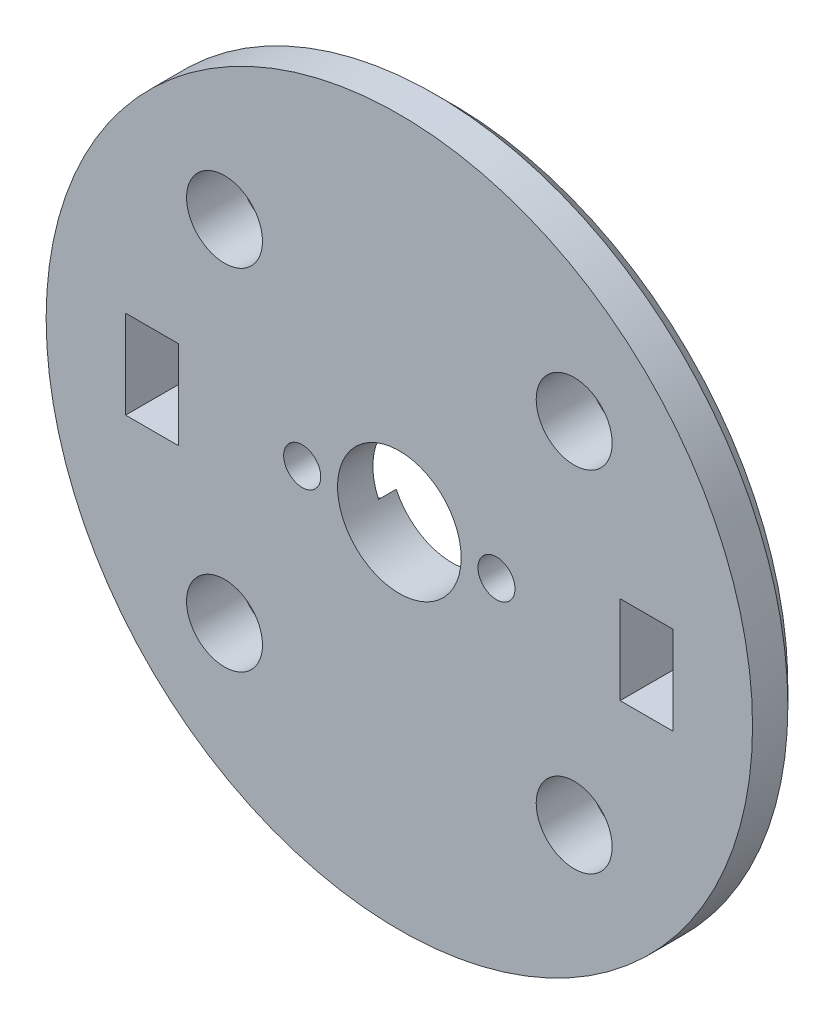
SolidWorks part; units mm, degrees
ref_plane "前视基准面" through (0, 0, 0) normal (0, 0, 1) x (1, 0, 0)
ref_plane "上视基准面" through (0, 0, 0) normal (0, 1, 0) x (1, 0, 0)
ref_plane "右视基准面" through (0, 0, 0) normal (1, 0, 0) x (0, 0, -1)
sketch "草图1" plane through (0, 0, 0) normal (0, 0, 1) x (1, 0, 0)
  circle A0 centre (0, 0) radius 20
  dimension "D1" = 40
extrude "凸台-拉伸1" add sketch "草图1" along normal blind 2
sketch "草图2" plane through (0, 0, 2) normal (0, 0, 1) x (1, 0, 0)
  circle A0 centre (0, 0) radius 3.5
  dimension "D1" = 7
extrude "切除-拉伸1" cut sketch "草图2" against normal blind 2
sketch "草图3" plane through (0, 0, 2) normal (0, 0, 1) x (1, 0, 0)
  circle A0 centre (-5.5, 0) radius 1.05
  circle A1 centre (5.5, 0) radius 1.05
  circle A2 centre (0, 0) radius 3.5 construction
  dimension "D1" = 2.1
  dimension "D2" = 2.1
  dimension "D3" = 11
  dimension "D4" = 5.5
  dimension "D5" = 5.5
extrude "切除-拉伸2" cut sketch "草图3" against normal blind 2
sketch "草图4" plane through (0, 0, 2) normal (0, 0, 1) x (1, 0, 0)
  circle A0 centre (0, 0) radius 7.7
  circle A1 centre (0, 0) radius 10
  dimension "D1" = 15.4
  dimension "D2" = 20
extrude "凸台-拉伸2" [suppressed] add sketch "草图4" along normal blind 10
sketch "草图5" plane through (0, 0, 0) normal (0, 0, -1) x (-1, 0, 0)
  circle A0 centre (0, 0) radius 20
  circle A1 centre (0, 0) radius 8.25
  dimension "D1" = 16.5
extrude "凸台-拉伸3" add sketch "草图5" along normal blind 1
sketch "草图6" plane through (0, 0, -1) normal (0, 0, -1) x (-1, 0, 0)
  circle A0 centre (0, 0) radius 14
  circle A1 centre (0, 0) radius 12
  circle A2 centre (0, 0) radius 16
  dimension "D1" = 28
  dimension "D2" = 24
  dimension "D3" = 32
sketch "草图7" [suppressed] plane through (0, 0, -1) normal (0, 0, -1) x (-1, 0, 0)
  circle A0 centre (0, 0) radius 11.25
  circle A1 centre (0, 0) radius 8.5
  dimension "D1" = 22.5
  dimension "D2" = 17
sketch "草图8" plane through (0, 0, 0) normal (0, 0, -1) x (-1, 0, 0)
  circle A0 centre (0, 0) radius 8.25
  arc A1 (-3.1761, -1.4704) -> (3.1761, -1.4704) centre (0, 0) ccw
  arc A2 (-3.1761, 1.4704) -> (-3.1761, -1.4704) centre (-5.5, 0) ccw
  arc A3 (3.1761, -1.4704) -> (3.1761, 1.4704) centre (5.5, 0) ccw
  arc A4 (3.1761, 1.4704) -> (-3.1761, 1.4704) centre (0, 0) ccw
  circle M1 centre (0, 0) radius 3.5
  circle M4 centre (0, 0) radius 8.25
  dimension "D1" = 16.5
extrude "凸台-拉伸4" add sketch "草图8" along normal blind 1 contours A3 A2 M1 M4 | A3 A0 A2 M1 region at (0, 4.8754, 0) region at (0, -4.8754, 0)
sketch "草图9" plane through (0, 0, -1) normal (0, 0, -1) x (-1, 0, 0)
  circle A0 centre (0, 0) radius 10.2
  circle A2 centre (0, 0) radius 7
  dimension "D1" = 20.4
  dimension "D2" = 14
extrude "切除-拉伸3" cut sketch "草图9" against normal blind 1.6
sketch "草图11" [suppressed] plane through (0, 0, 0.6) normal (0, 0, -1) x (-1, 0, 0)
  circle A0 centre (0, 0) radius 8.3
  circle A1 centre (0, 0) radius 11.5
  circle A2 centre (0, 0) radius 11.5
  dimension "D1" = 0
sketch "草图12" plane through (0, 0, 0.6) normal (0, 0, -1) x (-1, 0, 0)
  line L0 (6.3442, 2.9583) -> (9.2443, 4.3107)
  line L1 (6.3442, -2.9583) -> (9.2443, -4.3107)
  arc A0 (6.3442, 2.9583) -> (6.3442, -2.9583) centre (0, 0) cw
  circle A1 centre (0, 0) radius 7 construction
  arc A2 (9.2443, -4.3107) -> (9.2443, 4.3107) centre (0, 0) ccw
  circle A3 centre (0, 0) radius 10.2 construction
  dimension "D1" = 50
  dimension "D2" = 50
extrude "凸台-拉伸5" add sketch "草图12" along normal blind 1.6
pattern_circular "阵列(圆周)2" count 2 over 180 about axis through (0, 0, -1) along (0, 0, -1) of "凸台-拉伸5"
sketch "草图13" plane through (0, 0, 0) normal (0, 0, -1) x (-1, 0, 0)
  circle A0 centre (5.5, 0) radius 2.75
  circle A1 centre (-5.5, 0) radius 2.75
  dimension "D1" = 5.5
  dimension "D2" = 5.5
extrude "切除-拉伸4" cut sketch "草图13" along normal blind 1.6
fillet "圆角1" radius 1.5 8 edges at (9.2443, -4.3107, -0.2) (-9.2443, -4.3107, -0.2) (-6.3442, -2.9583, -0.2) (6.3442, -2.9583, -0.2) (9.2443, 4.3107, -0.2) (6.3442, 2.9583, -0.2) (-9.2443, 4.3107, -0.2) (-6.3442, 2.9583, -0.2)
sketch "草图14" plane through (0, 0, -1) normal (0, 0, -1) x (-1, 0, 0)
  line L0 (0, 0) -> (20, 0) construction
  line L1 (0, 0) -> (14.1421, -14.1421) construction
  circle A0 centre (9.8995, -9.8995) radius 2.15
  circle A1 centre (0, 0) radius 14 construction
  circle A2 centre (-9.8995, -9.8995) radius 2.15
  circle A3 centre (-9.8995, 9.8995) radius 2.15
  circle A4 centre (9.8995, 9.8995) radius 2.15
  point P19 (0, 0)
  dimension "D2" = 0
  dimension "D3" = 4.3
  dimension "D1" = 45
  dimension "D4" = 4
extrude "切除-拉伸5" cut sketch "草图14" against normal blind 10
sketch "草图15" plane through (0, 0, 2) normal (0, 0, 1) x (1, 0, 0)
  line L0 (0, 0) -> (29.4349, 0) construction
  line L1 (-12.5, -2.5) -> (-12.5, 2.5)
  line L2 (12.5, 2.5) -> (15.5, 2.5)
  line L3 (12.5, 2.5) -> (12.5, -2.5)
  line L4 (12.5, -2.5) -> (15.5, -2.5)
  line L5 (15.5, 2.5) -> (15.5, -2.5)
  line L6 (12.5, 2.5) -> (15.5, -2.5) construction
  line L7 (12.5, -2.5) -> (15.5, 2.5) construction
  line L8 (-12.5, -2.5) -> (-15.5, -2.5)
  line L9 (-15.5, -2.5) -> (-15.5, 2.5)
  line L10 (-12.5, 2.5) -> (-15.5, 2.5)
  circle A0 centre (0, 0) radius 14 construction
  point P1 (14, 0)
  point P16 (0, 0)
  dimension "D1" = 3
  dimension "D2" = 5
  dimension "D3" = 2
extrude "切除-拉伸6" cut sketch "草图15" against normal blind 10
sketch "草图16" [suppressed] plane through (0, 0, 2) normal (0, 0, 1) x (1, 0, 0)
  circle A1 centre (0, 0) radius 20
  circle A2 centre (0, 0) radius 20
  dimension "D1" = 0
sketch "草图17" [suppressed] plane through (0, 0, -1) normal (0, 0, -1) x (-1, 0, 0)
  circle A0 centre (0, 0) radius 20
  circle A1 centre (0, 0) radius 18
  dimension "D1" = 40
  dimension "D2" = 36
chamfer "倒角1" distance 1 angle 45 1 edges at (-20, 0, -1)
